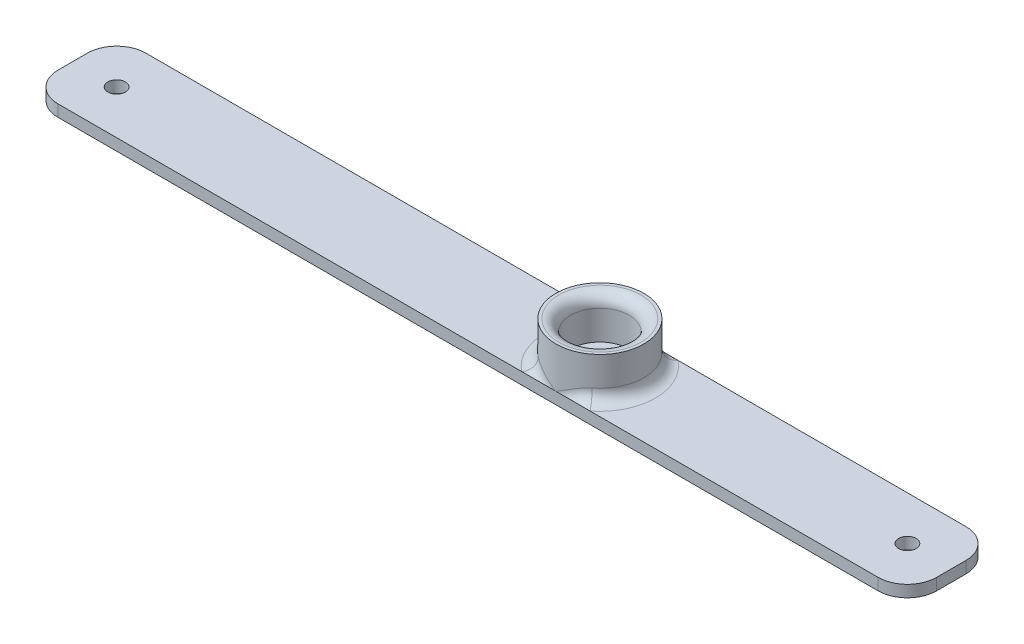
SolidWorks part; units mm, degrees
ref_plane "Front Plane" through (0, 0, 0) normal (0, 0, 1) x (1, 0, 0)
ref_plane "Top Plane" through (0, 0, 0) normal (0, 1, 0) x (1, 0, 0)
ref_plane "Right Plane" through (0, 0, 0) normal (1, 0, 0) x (0, 0, -1)
sketch "Sketch1" plane through (0, 0, 0) normal (0, 1, 0) x (1, 0, 0)
  line L5 (-7.5, 7.5) -> (142.5, 7.5)
  line L6 (-7.5, 7.5) -> (-7.5, -7.5)
  line L11 (-7.5, -7.5) -> (142.5, -7.5)
  line L12 (142.5, 7.5) -> (142.5, -7.5)
  circle A3 centre (0, 0) radius 1.5
  circle A4 centre (82.5, 0) radius 5
  circle A5 centre (135, 0) radius 1.5
  circle A6 centre (82.5, 0) radius 7.5
  point P11 (-7.5, 0)
  dimension "D3" = 10
  dimension "D6" = 15
  dimension "D2" = 3
  dimension "D5" = 3
  dimension "D1" = 82.5
  dimension "D4" = 52.5
  dimension "D7" = 7.5
  dimension "D8" = 7.5
extrude "Boss-Extrude1" add sketch "Sketch1" along normal blind 2 contours A6 L5 L6 L11 A3 | A6 A4 | A6 L11 L12 L5 A5 | A4 region at (34.7662, 0, 0) region at (115.2473, 0, 0) region at (87.6533, 0, -5.1533) region at (82.5, 0, 0)
extrude "Boss-Extrude2" add sketch "Sketch1<3>" along normal blind 7 from surface contours A6 A4 region at (87.6533, 0, -5.1533) starting at face at (67.5, 2, 0)
sketch "Sketch1<3>" plane through (0, 0, 0) normal (0, 1, 0) x (1, 0, 0) same geometry as "Sketch1"
fillet "Fillet1" radius 5 4 edges at (142.5, 1, 7.5) (142.5, 1, -7.5) (-7.5, 1, 7.5) (-7.5, 1, -7.5)
fillet "Fillet2" radius 2 2 edges at (90, 2, 0) (82.5, 9, 5)
